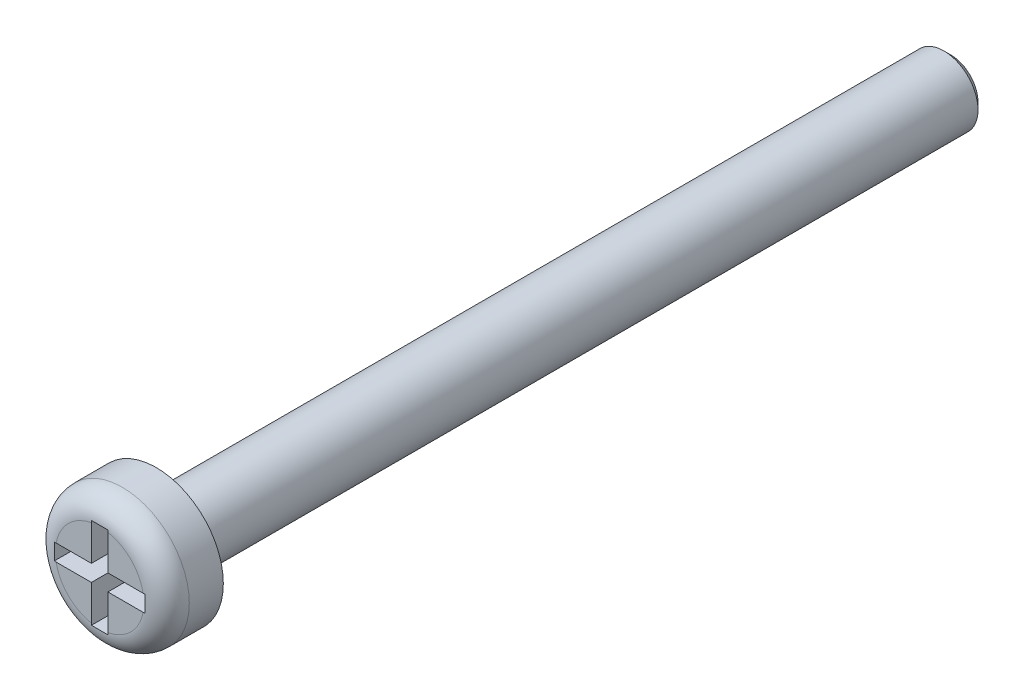
SolidWorks part; units mm, degrees
ref_plane "Front Plane" through (0, 0, 0) normal (0, 0, 1) x (1, 0, 0)
ref_plane "Top Plane" through (0, 0, 0) normal (0, 1, 0) x (1, 0, 0)
ref_plane "Right Plane" through (0, 0, 0) normal (1, 0, 0) x (0, 0, -1)
sketch "Sketch1" plane through (0, 0, 0) normal (0, 0, 1) x (1, 0, 0)
  circle A0 centre (0, 0) radius 2.95
  dimension "D1" = 5.9
extrude "Boss-Extrude1" add sketch "Sketch1" along normal blind 2.5
sketch "Sketch2" plane through (0, 0, 0) normal (0, 0, -1) x (-1, 0, 0)
  circle A0 centre (0, 0) radius 1.5
  dimension "D1" = 3
extrude "Boss-Extrude2" add sketch "Sketch2" along normal blind 35
chamfer "Chamfer1" distance 0.3 angle 45 1 edges at (-1.5, 0, -35)
sketch "Sketch3" plane through (0, 0, 2.5) normal (0, 0, 1) x (1, 0, 0)
  line L0 (0.3636, 0.3636) -> (2, 0.3636)
  line L1 (0.3636, -0.3636) -> (2, -0.3636)
  line L2 (-0.3636, 0.3636) -> (-0.3636, 2)
  line L3 (0.3636, 0.3636) -> (0.3636, 2)
  line L7 (-2, -0.3636) -> (-0.3636, -0.3636)
  line L8 (-2, -0.3636) -> (-2, 0.3636)
  line L9 (-2, 0.3636) -> (-0.3636, 0.3636)
  line L10 (2, -0.3636) -> (2, 0.3636)
  line L11 (-2, -0.3636) -> (2, 0.3636) construction
  line L12 (-2, 0.3636) -> (2, -0.3636) construction
  line L13 (-0.3636, -2) -> (0.3636, -2)
  line L14 (-0.3636, -2) -> (-0.3636, -0.3636)
  line L15 (-0.3636, 2) -> (0.3636, 2)
  line L16 (0.3636, -2) -> (0.3636, -0.3636)
  line L17 (-0.3636, -2) -> (0.3636, 2) construction
  line L18 (-0.3636, 2) -> (0.3636, -2) construction
  point P4 (0, 0)
  point P6 (0, 0)
  dimension "D1" = 4
extrude "Cut-Extrude1" cut sketch "Sketch3" against normal blind 2
fillet "Fillet1" radius 1 1 edges at (2.95, 0, 2.5)
